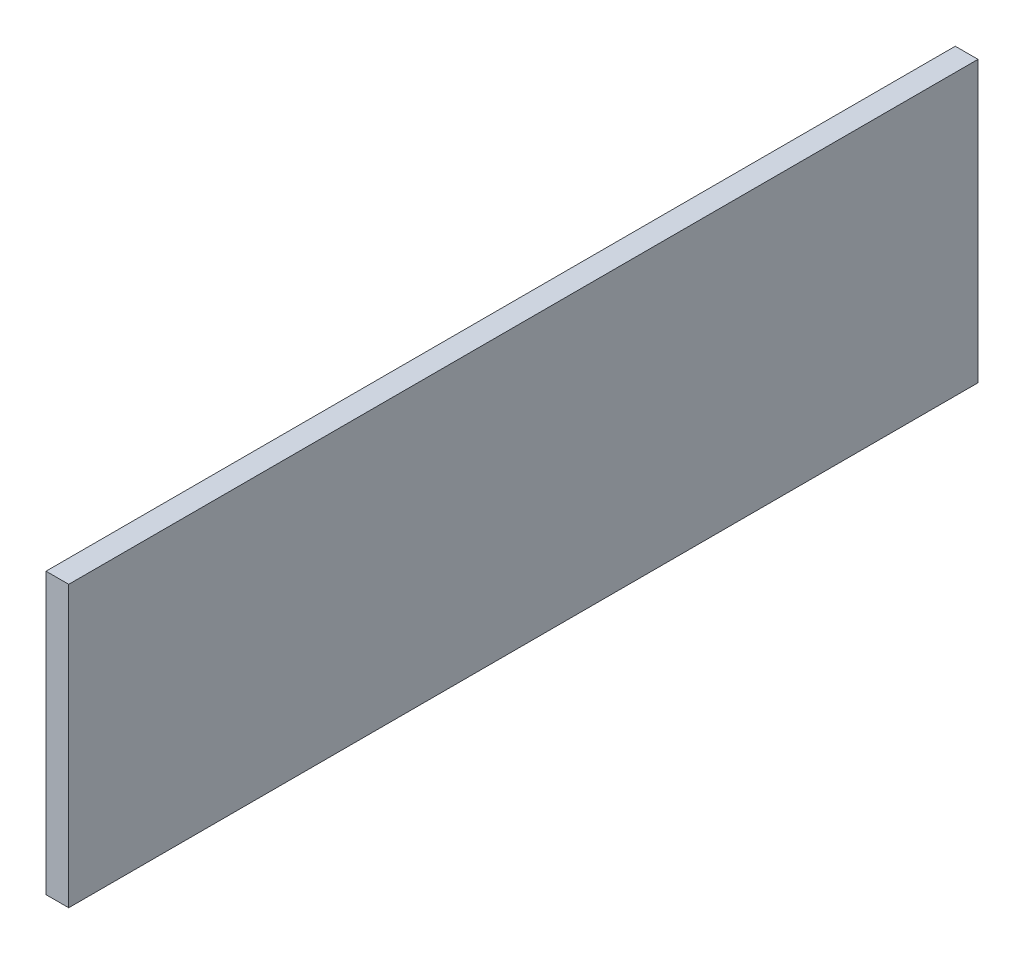
SolidWorks part; units mm, degrees
material "Oak"
ref_plane "Front" through (0, 0, 0) normal (0, 0, 1) x (1, 0, 0)
ref_plane "Top" through (0, 0, 0) normal (0, 1, 0) x (1, 0, 0)
ref_plane "Right" through (0, 0, 0) normal (1, 0, 0) x (0, 0, -1)
sketch "Sketch1" plane through (0, 0, 0) normal (0, 0, 1) x (1, 0, 0)
  line L0 (-240.475, 9.525) -> (240.475, 9.525)
  line L1 (-250, 0) -> (250, 0)
  line L2 (-250, 0) -> (-250, 500)
  line L3 (-250, 500) -> (250, 500)
  line L4 (250, 0) -> (250, 500)
  line L5 (240.475, 9.525) -> (240.475, 490.475)
  line L6 (-240.475, 490.475) -> (240.475, 490.475)
  line L7 (-240.475, 9.525) -> (-240.475, 490.475)
  line L8 (-142.3043, 490.475) -> (-142.3043, 373.0167) construction
  line L9 (-240.475, 373.0167) -> (240.475, 373.0167)
  line L10 (-240.475, 373.0167) -> (-240.475, 363.4917)
  line L11 (-240.475, 363.4917) -> (240.475, 363.4917)
  line L12 (240.475, 373.0167) -> (240.475, 363.4917)
  line L13 (-240.475, 246.0333) -> (240.475, 246.0333)
  line L14 (-240.475, 246.0333) -> (-240.475, 236.5083)
  line L15 (-240.475, 236.5083) -> (240.475, 236.5083)
  line L16 (240.475, 246.0333) -> (240.475, 236.5083)
  line L17 (-240.475, 119.05) -> (240.475, 119.05)
  line L18 (-240.475, 119.05) -> (-240.475, 109.525)
  line L19 (-240.475, 109.525) -> (240.475, 109.525)
  line L20 (240.475, 119.05) -> (240.475, 109.525)
  line L21 (-142.3043, 363.4917) -> (-142.3043, 246.0333) construction
  line L22 (-142.3043, 236.5083) -> (-142.3043, 119.05) construction
  line L23 (-240.475, 431.7458) -> (-86.5083, 431.7458) construction
  line L24 (-86.5083, 490.475) -> (-76.9833, 490.475)
  line L25 (-86.5083, 490.475) -> (-86.5083, 373.0167)
  line L26 (-86.5083, 373.0167) -> (-76.9833, 373.0167)
  line L27 (-76.9833, 490.475) -> (-76.9833, 373.0167)
  line L28 (76.9833, 490.475) -> (86.5083, 490.475)
  line L29 (76.9833, 490.475) -> (76.9833, 373.0167)
  line L30 (76.9833, 373.0167) -> (86.5083, 373.0167)
  line L31 (86.5083, 490.475) -> (86.5083, 373.0167)
  line L32 (-76.9833, 431.7458) -> (76.9833, 431.7458) construction
  line L33 (86.5083, 431.7458) -> (240.475, 431.7458) construction
  line L34 (-131.311, 490.475) -> (-131.311, 363.4917) construction
  dimension "D1" = 500
  dimension "D2" = 9.525
  dimension "D3" = 9.525
  dimension "D4" = 100
  dimension "D5" = 9.525
  dimension "D6" = 117.4583
  dimension "D7" = 117.4583
  dimension "D8" = 126.9833
  dimension "D9" = 153.9667
  dimension "D10" = 153.9667
  dimension "D11" = 153.9667
extrude "Boss-Extrude1" add sketch "Sketch1" along normal blind 381.25 contours L27 L6 L25 L9 region at (-81.7458, 431.7458, 0)
